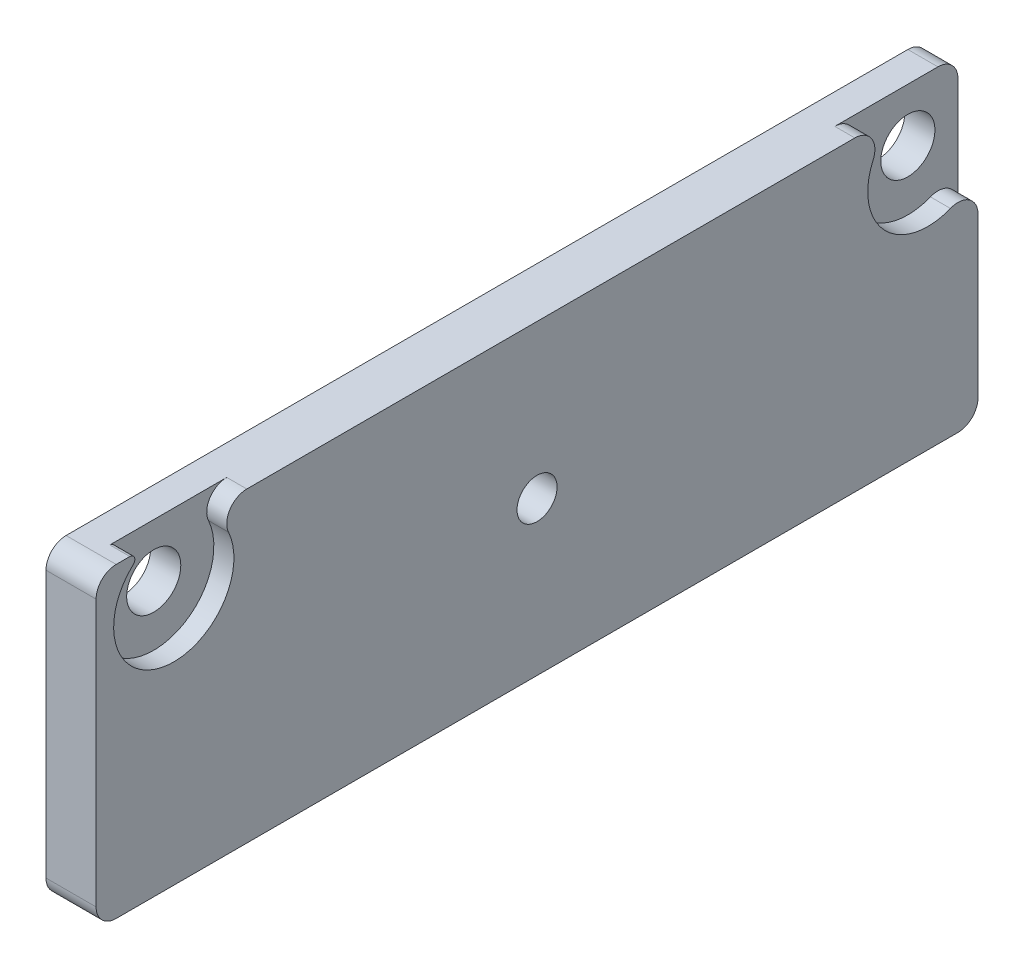
SolidWorks part; units mm, degrees
material "ABS"
ref_plane "Front Plane" through (0, 0, 0) normal (0, 0, 1) x (1, 0, 0)
ref_plane "Top Plane" through (0, 0, 0) normal (0, 1, 0) x (1, 0, 0)
ref_plane "Right Plane" through (0, 0, 0) normal (1, 0, 0) x (0, 0, -1)
sketch "Sketch1" plane through (0, 0, 0) normal (1, 0, 0) x (0, 0, -1)
  line L0 (-18.125, 5) -> (19.5, 5) construction
  line L1 (-22, -7.65) -> (22, -7.65)
  line L2 (-22, -7.65) -> (-22, 7.65)
  line L3 (-22, 7.65) -> (22, 7.65)
  line L4 (22, -7.65) -> (22, 7.65)
  line L5 (-22, -7.65) -> (22, 7.65) construction
  line L6 (-22, 7.65) -> (22, -7.65) construction
  circle A0 centre (0, 0) radius 1
  point P0 (0, 0)
  dimension "D6" = 2
  dimension "D1" = 15.3
  dimension "D2" = 44
  dimension "D3" = 2.65
  dimension "D4" = 3.875
  dimension "D5" = 2.5
extrude "Boss-Extrude1" add sketch "Sketch1" along normal blind 2.5
sketch "Sketch3" plane through (2.5, 0, 0) normal (1, 0, 0) x (0, 0, -1)
  point P0 (-18.125, 5)
  point P3 (19.5, 5)
hole_wizard "CBORE for M2.5 Pan Head Machine Screw1" positions "Sketch3" profile "Sketch4" counterbore size "M2.5" standard "ANSI Metric" end condition through all
sketch "Sketch4" plane through (2.5, 5, 18.125) normal (0, 1, 0) x (0, 0, -1)
  line L0 (0, 0) -> (0, 2.5)
  line L1 (0, 2.5) -> (1.35, 2.5)
  line L3 (1.35, 2.5) -> (1.35, 1)
  line L4 (1.35, 1) -> (3, 1)
  line L5 (3, 1) -> (3, 0)
  line L7 (3, 0) -> (0, 0)
  line L11 (0, -6.35) -> (0, 107.95) construction
  dimension "Thru Hole Dia." = 2.7
  dimension "Thru Hole Depth" = 2.5
  dimension "C'Bore Dia." = 6
  dimension "C'Bore Depth" = 1
sketch "Sketch5" plane through (2.5, 0, 0) normal (1, 0, 0) x (0, 0, -1)
  line L2 (-22, 7.65) -> (-22, -7.65)
  line L3 (-22, 7.65) -> (-22, -7.65)
  line L6 (22, 6.6583) -> (22, 7.65)
  line L7 (22, 6.6583) -> (22, 7.65)
  line L10 (22, 7.65) -> (20.9062, 7.65)
  line L11 (22, 7.65) -> (20.9062, 7.65)
  line L12 (-19.5312, 7.65) -> (-22, 7.65)
  line L13 (-19.5312, 7.65) -> (-22, 7.65)
  line L17 (18.0938, 7.65) -> (-16.7188, 7.65)
  line L18 (18.0938, 7.65) -> (-16.7188, 7.65)
  line L19 (-22, -7.65) -> (22, -7.65)
  line L20 (-22, -7.65) -> (22, -7.65)
  line L21 (22, -7.65) -> (22, 3.3417)
  line L22 (22, -7.65) -> (22, 3.3417)
  arc A1 (-19.5312, 7.65) -> (-16.7188, 7.65) centre (-18.125, 5) ccw
  arc A3 (22, 6.6583) -> (20.9062, 7.65) centre (19.5, 5) ccw
  arc A5 (22, 6.6583) -> (20.9062, 7.65) centre (19.5, 5) ccw
  arc A6 (-19.5312, 7.65) -> (-16.7188, 7.65) centre (-18.125, 5) ccw
  arc A8 (18.0938, 7.65) -> (22, 3.3417) centre (19.5, 5) ccw
  arc A9 (18.0938, 7.65) -> (22, 3.3417) centre (19.5, 5) ccw
  dimension "D1" = 0
  dimension "D2" = 0
extrude "Cut-Extrude1" cut sketch "Sketch5" against normal up to surface (1 mm away) contours A5 L7 L11 region at (2.5, 7.3473, -21.6672) up to face at (1.5, 5, 16.775)
fillet "Fillet1" radius 1 7 edges at (2, 7.65, -18.0938) (2, 7.65, 16.7188) (1.25, 7.65, 22) (0.75, 7.65, -22) (1.25, -7.65, -22) (1.25, -7.65, 22) (2, 3.3417, -22)
fillet "Fillet2" radius 0.25 1 edges at (2, 7.65, 19.5312)
